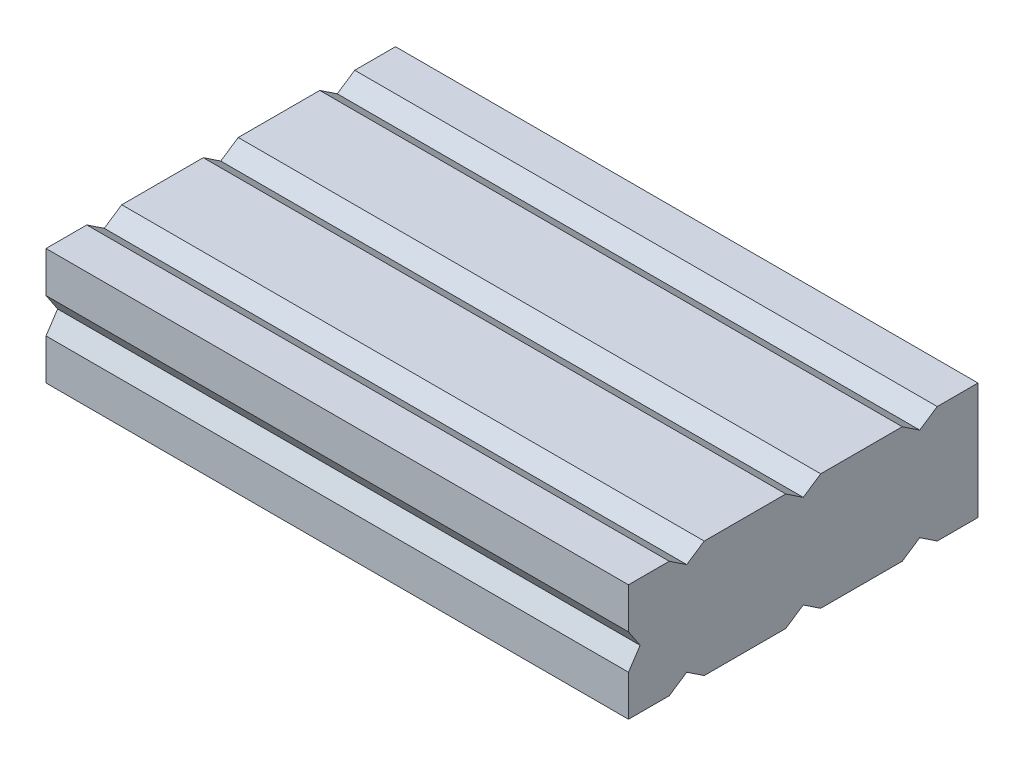
SolidWorks part; units mm, degrees
ref_plane "Front" through (0, 0, 0) normal (0, 0, 1) x (1, 0, 0)
ref_plane "Top" through (0, 0, 0) normal (0, 1, 0) x (1, 0, 0)
ref_plane "Right" through (0, 0, 0) normal (1, 0, 0) x (0, 0, -1)
sketch "Skizze1" plane through (0, 0, 0) normal (1, 0, 0) x (0, 0, -1)
  line L0 (-30, 10) -> (-30, -10) construction
  line L1 (-40, -10) -> (-33, -10)
  line L2 (-40, -10) -> (-40, -3)
  line L3 (-40, 10) -> (-33, 10)
  line L4 (40, -10) -> (40, -3)
  line L5 (-40, -10) -> (40, 10) construction
  line L6 (-40, 10) -> (40, -10) construction
  line L7 (-33, 10) -> (-30, 8)
  line L8 (-27, 10) -> (-30, 8)
  line L9 (0, 0) -> (-40, 0) construction
  line L10 (-7, 10) -> (-10, 8)
  line L11 (-13, 10) -> (-10, 8)
  line L12 (13, 10) -> (10, 8)
  line L13 (7, 10) -> (10, 8)
  line L14 (33, 10) -> (30, 8)
  line L15 (27, 10) -> (30, 8)
  line L16 (33, -10) -> (30, -8)
  line L17 (27, -10) -> (30, -8)
  line L18 (13, -10) -> (10, -8)
  line L19 (7, -10) -> (10, -8)
  line L20 (-7, -10) -> (-10, -8)
  line L21 (-13, -10) -> (-10, -8)
  line L22 (-33, -10) -> (-30, -8)
  line L23 (-27, -10) -> (-30, -8)
  line L24 (-40, 3) -> (-38, 0)
  line L25 (-40, -3) -> (-38, 0)
  line L26 (0, 0) -> (0, 10) construction
  line L27 (40, -3) -> (38, 0)
  line L28 (40, 3) -> (38, 0)
  line L29 (-30, 10) -> (-27, 10) construction
  line L30 (-27, 10) -> (-13, 10)
  line L31 (-33, 10) -> (-30, 10) construction
  line L32 (-40, 0) -> (-40, 3) construction
  line L33 (-40, 3) -> (-40, 10)
  line L34 (-40, -3) -> (-40, 0) construction
  line L35 (-33, -10) -> (-30, -10) construction
  line L36 (-27, -10) -> (-13, -10)
  line L37 (-30, -10) -> (-27, -10) construction
  line L38 (-13, -10) -> (-7, -10) construction
  line L39 (-7, -10) -> (7, -10)
  line L40 (7, -10) -> (13, -10) construction
  line L41 (13, -10) -> (27, -10)
  line L42 (-13, 10) -> (-7, 10) construction
  line L43 (-7, 10) -> (7, 10)
  line L44 (7, 10) -> (13, 10) construction
  line L45 (13, 10) -> (27, 10)
  line L46 (27, 10) -> (33, 10) construction
  line L47 (33, 10) -> (40, 10)
  line L48 (27, -10) -> (33, -10) construction
  line L49 (33, -10) -> (40, -10)
  line L50 (40, -3) -> (40, 3) construction
  line L51 (40, 3) -> (40, 10)
  line L52 (20, -10) -> (20, 10)
  point P0 (0, 0)
  dimension "D1" = 80
  dimension "D2" = 20
  dimension "D3" = 6
  dimension "D4" = 10
  dimension "D6" = 20
  dimension "D7" = 2
  dimension "D8" = 6
  dimension "D9" = 2
  dimension "D5" = 4
extrude "Aufsatz-Linear austragen1" add sketch "Skizze1" along normal blind 100 contours L41 L52 L45 L12 L13 L43 L10 L11 L30 L8 L7 L3 L33 L24 L25 L2 L1 L22 L23 L36 L21 L20 L39 L19 L18 region at (0, 0, 9.848)
